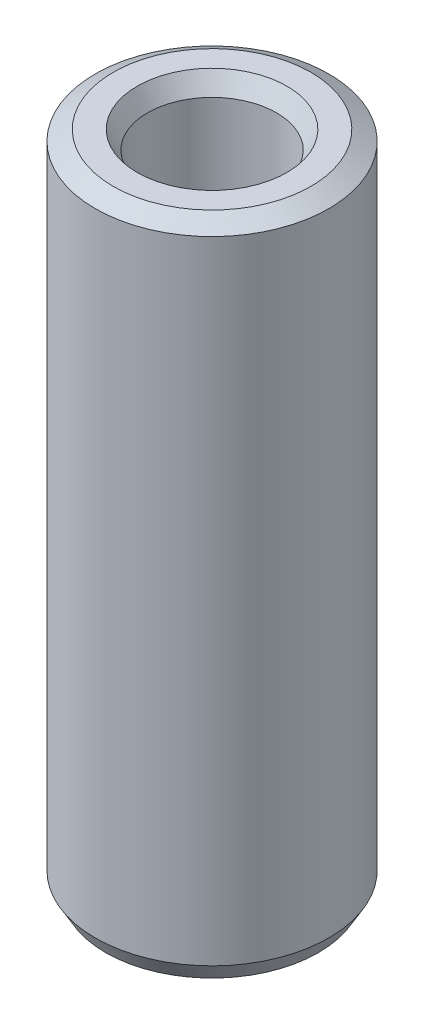
SolidWorks part; units mm, degrees
ref_plane "Front Plane" through (0, 0, 0) normal (0, 0, 1) x (1, 0, 0)
ref_plane "Top Plane" through (0, 0, 0) normal (0, 1, 0) x (1, 0, 0)
ref_plane "Right Plane" through (0, 0, 0) normal (1, 0, 0) x (0, 0, -1)
sketch "Sketch1" plane through (0, 0, 0) normal (0, 1, 0) x (1, 0, 0)
  circle A0 centre (0, 0) radius 5
  dimension "SLEEVE_OD" = 10
extrude "Boss-Extrude1" add sketch "Sketch1" along normal blind 28.254
sketch "Sketch2" plane through (0, 0, 0) normal (0, 1, 0) x (1, 0, 0)
  circle A0 centre (0, 0) radius 2.7622
  dimension "BORE_D" = 5.5244
extrude "Cut-Extrude1" cut sketch "Sketch2" along normal through all
chamfer "Chamfer1" distance 0.4428 angle 60 4 edges at (0, 28.254, 2.7622) (0, 0, 2.7622) (0, 0, 5) (0, 28.254, 5) first distance on face at (0, 28.254, 2.7622) first distance on face at (0, 0, 2.7622) first distance on face at (0, 28.254, 5)
